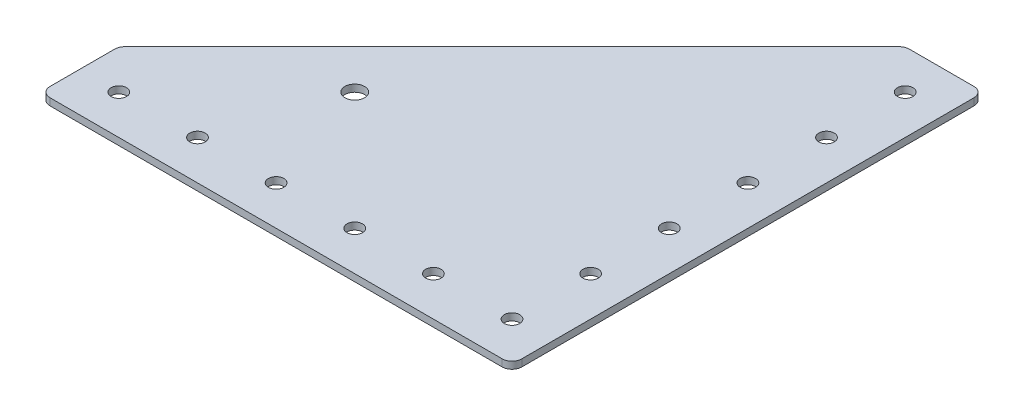
SolidWorks part; units mm, degrees
ref_plane "Front Plane" through (0, 0, 0) normal (0, 0, 1) x (1, 0, 0)
ref_plane "Top Plane" through (0, 0, 0) normal (0, 1, 0) x (1, 0, 0)
ref_plane "Right Plane" through (0, 0, 0) normal (1, 0, 0) x (0, 0, -1)
sketch "Sketch1" plane through (0, 0, 0) normal (0, 1, 0) x (1, 0, 0)
  line L0 (0, 0) -> (0, 152.4)
  line L1 (0, 152.4) -> (-25.4, 152.4)
  line L2 (-25.4, 152.4) -> (-152.4, 25.4)
  line L3 (-152.4, 25.4) -> (-152.4, 0)
  line L4 (-152.4, 0) -> (0, 0)
  circle A0 centre (-12.7, 12.7) radius 2.4892
  circle A1 centre (-38.1, 12.7) radius 2.4892
  circle A2 centre (-63.5, 12.7) radius 2.4892
  circle A3 centre (-88.9, 12.7) radius 2.4892
  circle A4 centre (-114.3, 12.7) radius 2.4892
  circle A5 centre (-12.7, 38.1) radius 2.4892
  circle A6 centre (-12.7, 63.5) radius 2.4892
  circle A7 centre (-12.7, 88.9) radius 2.4892
  circle A8 centre (-12.7, 114.3) radius 2.4892
  circle A9 centre (-139.7, 12.7) radius 2.4892
  circle A13 centre (-12.7, 139.7) radius 2.4892
  circle A17 centre (-101.6, 50.8) radius 3.175
  dimension "D4" = 12.7
  dimension "D5" = 12.7
  dimension "D11" = 6.35
  dimension "D1" = 152.4
  dimension "D2" = 25.4
  dimension "D3" = 152.4
  dimension "D8" = 101.6
  dimension "D9" = 50.8
  dimension "D10" = 25.4
  dimension "D6" = 6
  dimension "D7" = 6
extrude "Boss-Extrude2" add sketch "Sketch1" along normal mid plane 2.286
fillet "Fillet1" radius 3.175 2 edges at (0, 0, 0) (-152.4, 0, 0)
fillet "Fillet2" radius 3.175 3 edges at (-152.4, 0, -25.4) (-25.4, 0, -152.4) (0, 0, -152.4)
